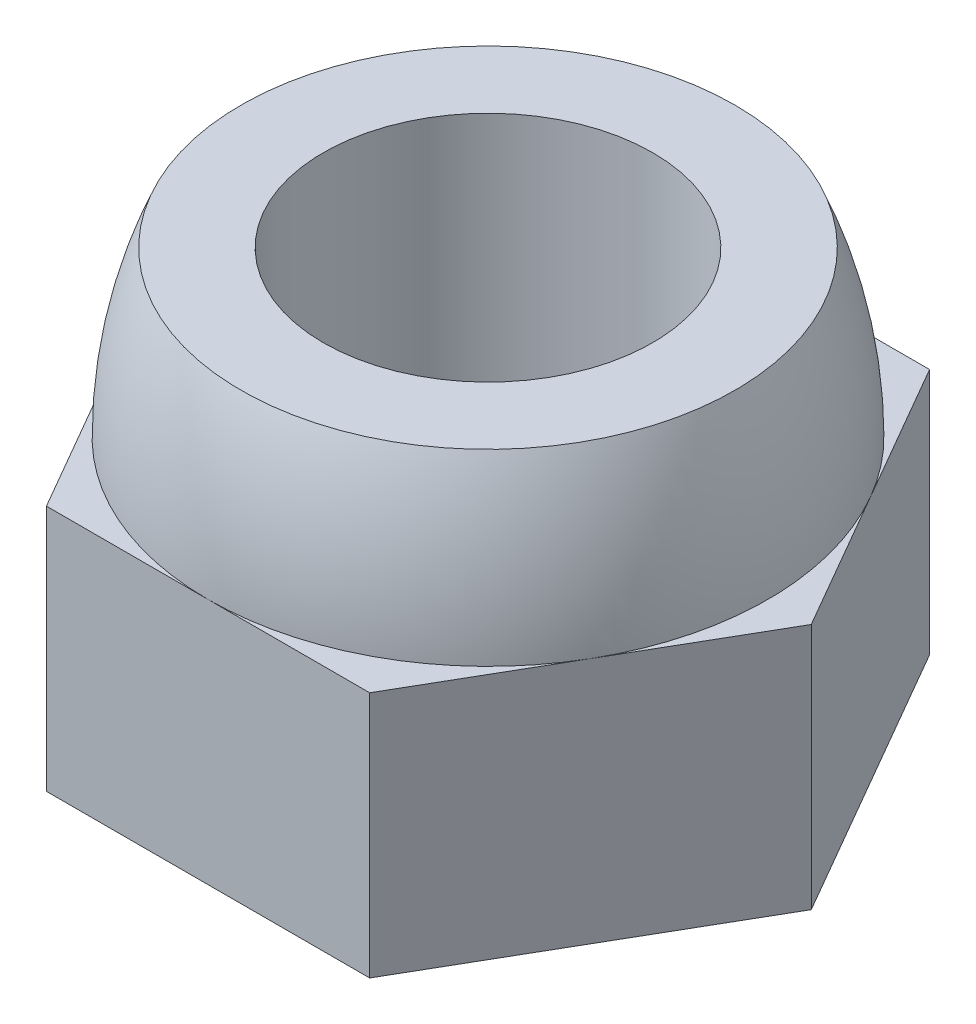
SolidWorks part; units mm, degrees
ref_plane "Front Plane" through (0, 0, 0) normal (0, 0, 1) x (1, 0, 0)
ref_plane "Top Plane" through (0, 0, 0) normal (0, 1, 0) x (1, 0, 0)
ref_plane "Right Plane" through (0, 0, 0) normal (1, 0, 0) x (0, 0, -1)
sketch "Sketch1" plane through (0, 0, 0) normal (0, 1, 0) x (1, 0, 0)
  line L1 (-1.963, -3.4) -> (1.963, -3.4)
  line L2 (1.963, -3.4) -> (3.926, 0)
  line L3 (3.926, 0) -> (1.963, 3.4)
  line L4 (1.963, 3.4) -> (-1.963, 3.4)
  line L5 (-1.963, 3.4) -> (-3.926, 0)
  line L6 (-3.926, 0) -> (-1.963, -3.4)
  circle A0 centre (0, 0) radius 3.4 construction
  circle A1 centre (0, 0) radius 2
  dimension "D1" = 6.8
  dimension "D2" = 4
extrude "Boss-Extrude1" add sketch "Sketch1" along normal blind 3
sketch "Sketch2" plane through (0, 0, 0) normal (1, 0, 0) x (0, 0, -1)
  line L0 (-2, 3) -> (-2, 5)
  line L1 (-2, 5) -> (-3, 5)
  line L2 (-3.4, 3) -> (0, 3) construction
  line L3 (-3.4, 3) -> (-2, 3)
  line L4 (-3.4, 3) -> (-3.4, 1.9937) construction
  line L5 (-3.4, 0) -> (0, 0) construction
  line L6 (0, 0) -> (0, 5.124) construction
  arc A0 (-3, 5) -> (-3.4, 3) centre (1.8, 3) ccw
  dimension "D1" = 5
  dimension "D2" = 1
revolve "Revolve1" add sketch "Sketch2" angle 360 about L6
